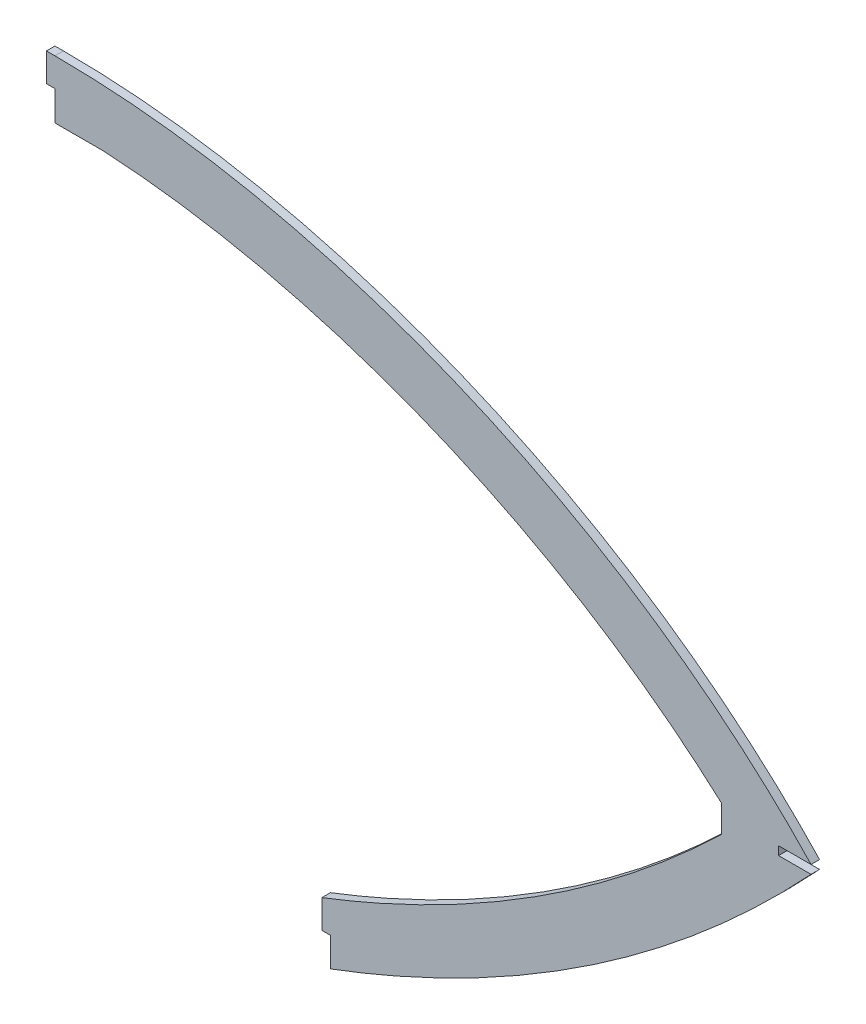
SolidWorks part; units mm, degrees
material "birch 3mm plywood"
ref_plane "Front" through (0, 0, 0) normal (0, 0, 1) x (1, 0, 0)
ref_plane "Top" through (0, 0, 0) normal (0, 1, 0) x (1, 0, 0)
ref_plane "Right" through (0, 0, 0) normal (1, 0, 0) x (0, 0, -1)
sketch "Sketch1" plane through (0, 0, 0) normal (0, 0, 1) x (1, 0, 0)
  line L2 (162, 160.5) -> (159, 160.5)
  line L3 (159, 160.5) -> (159, 150.5)
  line L4 (159, 150.5) -> (162, 150.5)
  line L5 (428.2878, 47) -> (416.8417, 47)
  line L6 (429.6834, 47.05) -> (162, 47.05) construction
  line L7 (416.8417, 47) -> (416.8417, 44)
  line L8 (416.8417, 44) -> (428.2966, 44)
  line L9 (162, 44.05) -> (429.6834, 44.05) construction
  line L10 (179.0354, 140.0216) -> (179.0354, 140.0216)
  line L11 (179.0354, 140.0216) -> (179.0354, 140.0216)
  line L12 (179.0354, 140.0216) -> (179.0354, 140.0216)
  line L13 (396.8417, 49.8799) -> (396.8417, 49.8799)
  line L14 (396.8417, 49.8799) -> (396.8417, 40.4728)
  line L15 (396.8417, 40.4728) -> (396.8417, 40.4728)
  line L16 (179.0354, 140.0216) -> (162, 140.0216)
  line L18 (162, 140.0216) -> (162, 150.5)
  line L19 (259, -69.5) -> (259, -59.2433)
  line L21 (259, -59.2433) -> (256, -59.2433)
  line L22 (256, -50.5) -> (256, -62.5) construction
  line L23 (256, -59.2433) -> (256, -49.2433)
  line L24 (256, -40.5) -> (256, -50.5) construction
  parabola Q1 (429.6834, 45.55) -> (259, -69.5) focus (230.1807, 156.1498) apex (350.0904, -22.916) construction
  parabola Q2 (428.2966, 44) -> (259, -69.5) focus (230.0403, 156.4144) apex (350.0839, -22.9206)
  spline S0 degree 1 poles (179.0354, 140.0216) (396.8417, 49.8799) knots 0 0 1 1 construction
  spline S1 degree 3 poles (987.524, -1569.8926) (-2032.9621, 1419.0502) (2883.4159, -234.996) (-1253.1235, -876.8067) knots -3.084543 -3.084543 -3.084543 -3.084543 3.933313 3.933313 3.933313 3.933313 only from (162, 160.5) to (429.6834, 45.55) construction
  spline S2 degree 3 poles (162, 160.5) (257.402, 160.5207) (362.2111, 117.35) (428.2878, 47) knots 0 0 0 0 0.993096 0.993096 0.993096 0.993096
  spline S3 degree 1 poles (396.8417, 40.4728) (251.9791, -50.7728) knots 0 0 1 1 construction
  spline S4 degree 3 poles (179.0354, 140.0216) (181.4518, 139.8872) (186.2712, 139.5636) (195.9767, 138.6926) (208.1599, 137.1905) (222.8333, 134.7367) (242.3999, 130.613) (266.7477, 123.8921) (295.4132, 113.4313) (323.1566, 100.6949) (345.203, 88.2923) (362.0163, 77.366) (374.171, 68.6867) (383.882, 61.0677) (391.3843, 54.7451) (395.0337, 51.5181) (396.8417, 49.8799) knots 0.062605 0.062605 0.062605 0.062605 0.088989 0.115372 0.168139 0.220906 0.273673 0.379207 0.484741 0.590275 0.695809 0.748576 0.801343 0.85411 0.880493 0.906877 0.906877 0.906877 0.906877
  spline S5 degree 3 poles (396.8417, 40.4728) (394.239, 37.9596) (388.9614, 32.9903) (378.2295, 23.3874) (364.4299, 11.9611) (347.2661, -0.8173) (329.4875, -12.6724) (311.0878, -23.6078) (292.0612, -33.6267) (275.6705, -41.2161) (262.2468, -46.8269) (255.4071, -49.4876) (251.9791, -50.7728) knots 0.498678 0.498678 0.498678 0.498678 0.498869 0.49906 0.499441 0.499822 0.500204 0.500585 0.500966 0.501348 0.501538 0.501729 0.501729 0.501729 0.501729 only from (396.8417, 40.4728) to (256, -49.2433)
  dimension "D1" = 20
  dimension "D2" = 10
extrude "Boss-Extrude1" add sketch "Sketch1" along normal mid plane 3 contours L16 L18 L4 L3 L2 S2 L5 L7 L8 Q2 L19 L21 L23 S5 L15 L14 L13 S4
